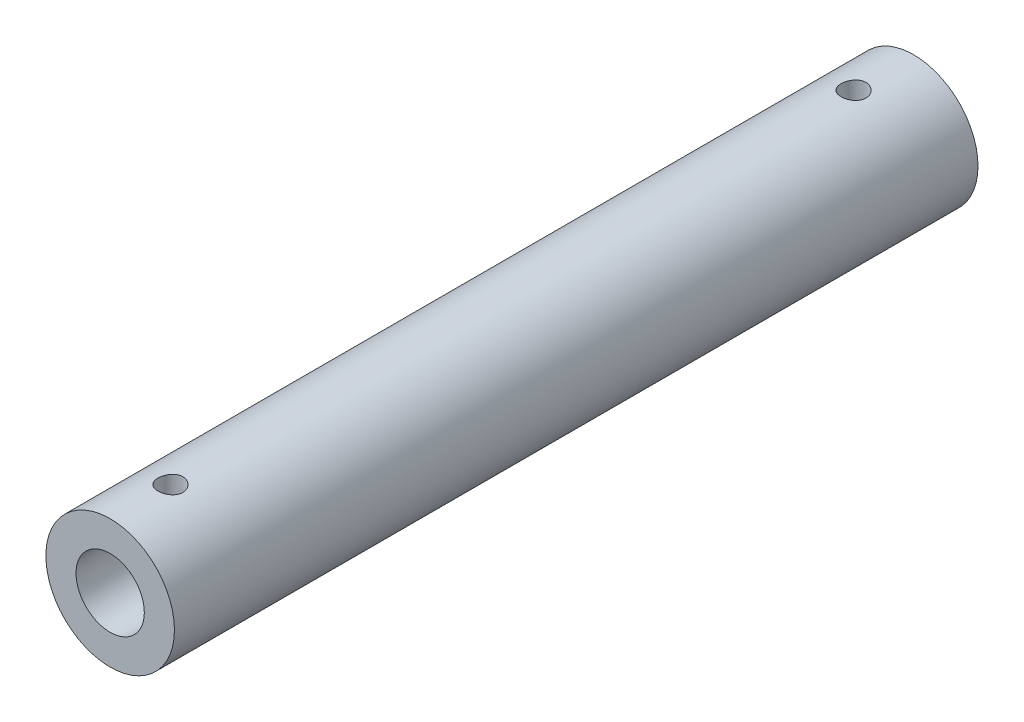
SolidWorks part; units mm, degrees
ref_plane "Front Plane" through (0, 0, 0) normal (0, 0, 1) x (1, 0, 0)
ref_plane "Top Plane" through (0, 0, 0) normal (0, 1, 0) x (1, 0, 0)
ref_plane "Right Plane" through (0, 0, 0) normal (1, 0, 0) x (0, 0, -1)
sketch "Sketch2" plane through (0, 0, 0) normal (0, 0, 1) x (1, 0, 0)
  circle A0 centre (0, 0) radius 16
  circle A1 centre (0, 0) radius 8.5
  dimension "D1" = 32
  dimension "D2" = 7.5
extrude "Boss-Extrude1" add sketch "Sketch2" along normal blind 100 and the other way blind 100
sketch "Sketch4" plane through (0, 0, 0) normal (0, 1, 0) x (1, 0, 0)
  line L0 (-16, -100) -> (16, -100) construction
  circle A0 centre (0, -85) radius 3.1
  dimension "D1" = 6.2
  dimension "D2" = 15
extrude "Cut-Extrude1" cut sketch "Sketch4" along normal through all
mirror "Mirror1" about plane through (0, 0, 0) normal (0, 0, 1) of "Cut-Extrude1"
